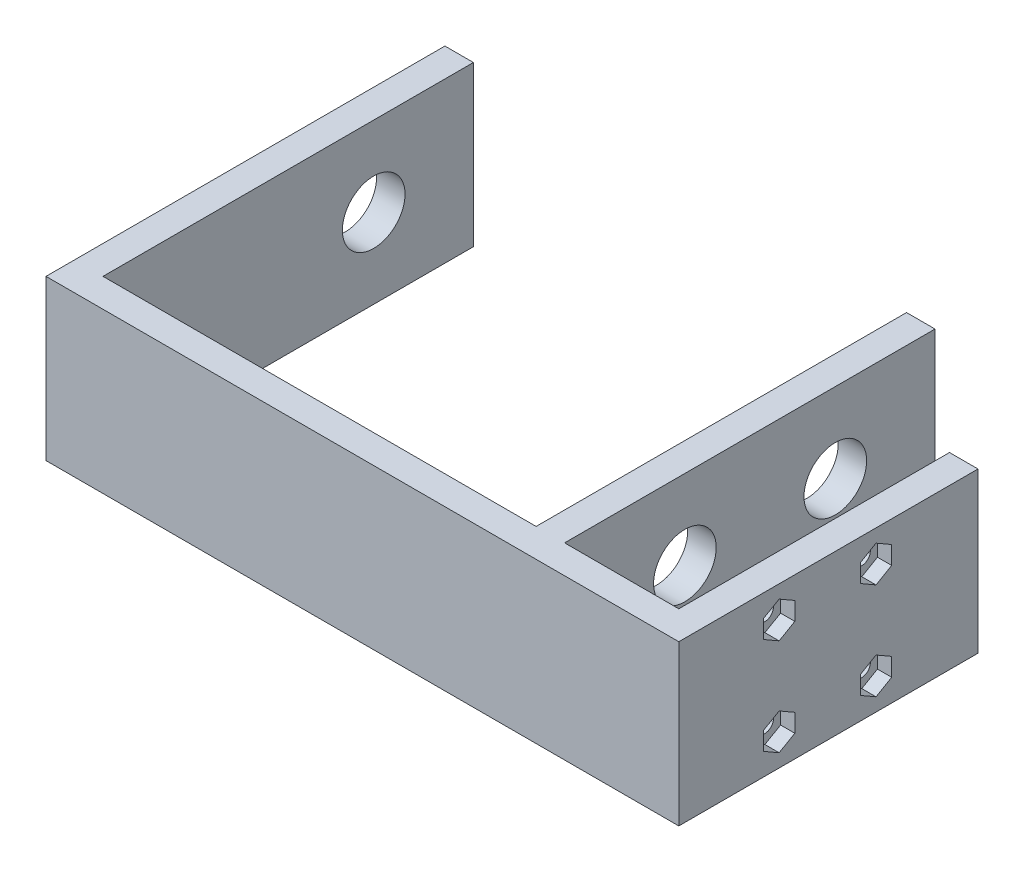
SolidWorks part; units mm, degrees
ref_plane "Front Plane" through (0, 0, 0) normal (0, 0, 1) x (1, 0, 0)
ref_plane "Top Plane" through (0, 0, 0) normal (0, 1, 0) x (1, 0, 0)
ref_plane "Right Plane" through (0, 0, 0) normal (1, 0, 0) x (0, 0, -1)
sketch "Sketch1" plane through (0, 0, 0) normal (0, 1, 0) x (1, 0, 0)
  line L0 (-35, -22.5) -> (-35, 22.5) construction
  line L1 (-30, -17.5) -> (30, -17.5) construction
  line L2 (-30, -17.5) -> (-30, 17.5) construction
  line L3 (-30, 17.5) -> (30, 17.5) construction
  line L4 (30, -17.5) -> (30, 17.5) construction
  line L5 (-30, -17.5) -> (30, 17.5) construction
  line L6 (-30, 17.5) -> (30, -17.5) construction
  line L7 (-35, 22.5) -> (35, 22.5) construction
  line L8 (35, -22.5) -> (35, 22.5) construction
  line L9 (-35, -22.5) -> (35, -22.5) construction
  line L10 (35, 0) -> (38, 0) construction
  line L11 (-35, 0) -> (-38, 0) construction
  line L12 (38, 0) -> (38, -22.5)
  line L13 (38, -22.5) -> (38, -47.5)
  line L14 (-38, 0) -> (-38, -22.5)
  line L15 (-38, -22.5) -> (-38, -47.5)
  line L16 (-38, -47.5) -> (38, -47.5)
  line L17 (38, 0) -> (38, 17.5)
  line L18 (-38, 0) -> (-38, 17.5)
  line L19 (-43, 0) -> (-43, 17.5)
  line L20 (-43, 0) -> (-43, -22.5)
  line L21 (-43, -22.5) -> (-43, -52.5)
  line L22 (-43, -52.5) -> (43, -52.5)
  line L23 (43, -22.5) -> (43, -52.5) construction
  line L24 (43, 0) -> (43, -22.5)
  line L25 (43, 0) -> (43, 17.5)
  line L26 (-38, 17.5) -> (-43, 17.5)
  line L27 (38, 17.5) -> (43, 17.5)
  line L28 (63.04, -47.5) -> (63.04, 0)
  line L29 (43, -52.5) -> (63.04, -52.5)
  line L31 (43, -47.5) -> (63.04, -47.5)
  line L32 (63.04, -52.5) -> (63.04, -47.5) construction
  line L33 (63.04, -52.5) -> (68.04, -52.5)
  line L34 (63.04, -52.5) -> (63.04, 0) construction
  line L35 (63.04, 0) -> (68.04, 0)
  line L36 (68.04, -52.5) -> (68.04, 0)
  line L37 (43, -47.5) -> (43, 17.5)
  point P0 (0, 0)
  point P10 (35, 0)
  point P11 (0, -22.5)
  point P12 (0, 22.5)
  point P13 (-35, 0)
  point P35 (0, 0)
  dimension "D1" = 60
  dimension "D2" = 35
  dimension "D4" = 3
  dimension "D5" = 25
  dimension "D7" = 20.04
  dimension "D8" = 5
  dimension "D3" = 5
  dimension "D6" = 5
extrude "Boss-Extrude1" add sketch "Sketch1" along normal mid plane 28 contours L31 L37 L24 L25 L27 L17 L12 L13 L16 L15 L14 L18 L26 L19 L20 L21 L22 L29 L33 L36 L35 L28 region at (39.3126, 0, -8.75)
sketch "Sketch2" plane through (43, 0, 0) normal (1, 0, 0) x (0, 0, -1)
  line L0 (-23.594, 0) -> (-26.9808, 0) construction
  line L1 (-23.594, 0) -> (-26.394, 0) construction
  line L4 (-47.5, -14) -> (17.5, -14)
  line L5 (17.5, -14) -> (17.5, 14)
  line L6 (-47.5, -14) -> (17.5, -14)
  line L7 (17.5, 14) -> (-47.5, 14)
  line L9 (17.5, -14) -> (17.5, 14)
  line L14 (17.5, 14) -> (-47.5, 14)
  line L15 (-47.5, 14) -> (-47.5, -14)
  line L16 (-47.5, 14) -> (-47.5, -14)
  circle A0 centre (0, 0) radius 5.5
  circle A1 centre (0, 0) radius 23.594 construction
  circle A2 centre (-26.394, 0) radius 3.3868 construction
  circle A3 centre (-26.9808, 0) radius 3.3867 construction
  circle A4 centre (-26.394, 0) radius 5.5
  dimension "D2" = 11
  dimension "D3" = 47.188
  dimension "D4" = 3.3868
  dimension "D5" = 2.8
  dimension "D1" = 0
extrude "Cut-Extrude1" cut sketch "Sketch2" against normal up to surface (86 mm away) contours A0 up to face at (-43, 0, 17.5)
sketch "Sketch3" plane through (43, 0, 0) normal (1, 0, 0) x (0, 0, -1)
  circle A0 centre (-26.394, 0) radius 5.5 construction
  circle A1 centre (-26.394, 0) radius 5.5
extrude "Cut-Extrude2" cut sketch "Sketch3" against normal up to next
sketch "Sketch4" plane through (63.04, 0, 0) normal (-1, 0, 0) x (0, 0, 1)
  line L1 (14.894, -11.5) -> (37.894, -11.5)
  line L2 (14.894, -11.5) -> (14.894, 11.5)
  line L3 (14.894, 11.5) -> (37.894, 11.5)
  line L4 (37.894, -11.5) -> (37.894, 11.5)
  line L5 (14.894, -11.5) -> (37.894, 11.5) construction
  line L6 (14.894, 11.5) -> (37.894, -11.5) construction
  line L7 (17.894, -8.5) -> (34.894, -8.5) construction
  line L8 (17.894, -8.5) -> (17.894, 8.5) construction
  line L9 (17.894, 8.5) -> (34.894, 8.5) construction
  line L10 (34.894, -8.5) -> (34.894, 8.5) construction
  line L11 (17.894, -8.5) -> (34.894, 8.5) construction
  line L12 (17.894, 8.5) -> (34.894, -8.5) construction
  circle A0 centre (17.894, 8.5) radius 1.85
  circle A1 centre (26.394, 0) radius 3
  circle A2 centre (26.394, 0) radius 3 construction
  circle A3 centre (34.894, 8.5) radius 1.85
  circle A4 centre (34.894, -8.5) radius 1.85
  circle A5 centre (17.894, -8.5) radius 1.85
  dimension "D6" = 3.7
  dimension "D2" = 23
  dimension "D3" = 23
  dimension "D4" = 17
  dimension "D5" = 17
  dimension "D1" = 0
sketch "Sketch6" plane through (68.04, 0, 0) normal (1, 0, 0) x (0, 0, -1)
  line L0 (-34.894, -5.2091) -> (-37.744, -6.8546) construction
  line L1 (-34.894, -5.3246) -> (-37.644, -6.9123)
  line L2 (-37.644, -6.9123) -> (-37.644, -10.0877)
  line L3 (-37.644, -10.0877) -> (-34.894, -11.6754)
  line L4 (-34.894, -11.6754) -> (-32.144, -10.0877)
  line L5 (-32.144, -10.0877) -> (-32.144, -6.9123)
  line L6 (-32.144, -6.9123) -> (-34.894, -5.3246)
  line L7 (-37.744, -6.8546) -> (-37.744, -10.1454) construction
  line L8 (-37.744, -10.1454) -> (-34.894, -11.7909) construction
  line L9 (-34.894, -11.7909) -> (-32.044, -10.1454) construction
  line L10 (-32.044, -10.1454) -> (-32.044, -6.8546) construction
  line L11 (-32.044, -6.8546) -> (-34.894, -5.2091) construction
  line L12 (-26.394, 1.435) -> (-26.394, -1.435) construction
  line L13 (-20.744, -6.8546) -> (-17.894, -5.2091) construction
  line L14 (-27.8, 0) -> (-24.988, 0) construction
  line L15 (-20.744, -10.1454) -> (-20.744, -6.8546) construction
  line L52 (-17.894, -11.7909) -> (-20.744, -10.1454) construction
  line L53 (-15.044, -10.1454) -> (-17.894, -11.7909) construction
  line L54 (-15.044, -6.8546) -> (-15.044, -10.1454) construction
  line L55 (-17.894, -5.2091) -> (-15.044, -6.8546) construction
  line L56 (-20.644, -6.9123) -> (-17.894, -5.3246)
  line L57 (-20.644, -10.0877) -> (-20.644, -6.9123)
  line L58 (-17.894, -11.6754) -> (-20.644, -10.0877)
  line L59 (-15.144, -10.0877) -> (-17.894, -11.6754)
  line L60 (-15.144, -6.9123) -> (-15.144, -10.0877)
  line L61 (-17.894, -5.3246) -> (-15.144, -6.9123)
  line L62 (-17.894, 5.2091) -> (-15.044, 6.8546) construction
  line L63 (-15.044, 6.8546) -> (-15.044, 10.1454) construction
  line L64 (-15.044, 10.1454) -> (-17.894, 11.7909) construction
  line L65 (-17.894, 11.7909) -> (-20.744, 10.1454) construction
  line L66 (-20.744, 10.1454) -> (-20.744, 6.8546) construction
  line L67 (-20.744, 6.8546) -> (-17.894, 5.2091) construction
  line L68 (-32.044, 6.8546) -> (-34.894, 5.2091) construction
  line L69 (-32.044, 10.1454) -> (-32.044, 6.8546) construction
  line L70 (-34.894, 11.7909) -> (-32.044, 10.1454) construction
  line L71 (-37.744, 10.1454) -> (-34.894, 11.7909) construction
  line L72 (-37.744, 6.8546) -> (-37.744, 10.1454) construction
  line L73 (-34.894, 5.2091) -> (-37.744, 6.8546) construction
  line L74 (-17.894, 5.3246) -> (-15.144, 6.9123)
  line L75 (-15.144, 6.9123) -> (-15.144, 10.0877)
  line L76 (-15.144, 10.0877) -> (-17.894, 11.6754)
  line L77 (-17.894, 11.6754) -> (-20.644, 10.0877)
  line L78 (-20.644, 10.0877) -> (-20.644, 6.9123)
  line L79 (-20.644, 6.9123) -> (-17.894, 5.3246)
  line L80 (-32.144, 6.9123) -> (-34.894, 5.3246)
  line L81 (-32.144, 10.0877) -> (-32.144, 6.9123)
  line L82 (-34.894, 11.6754) -> (-32.144, 10.0877)
  line L83 (-37.644, 10.0877) -> (-34.894, 11.6754)
  line L84 (-37.644, 6.9123) -> (-37.644, 10.0877)
  line L85 (-34.894, 5.3246) -> (-37.644, 6.9123)
  circle A3 centre (-34.894, -8.5) radius 1.85 construction
  circle A7 centre (-34.894, -8.5) radius 1.85 construction
  circle A8 centre (-34.894, -8.5) radius 2.75 construction
  circle A16 centre (-17.894, -8.5) radius 2.75 construction
  circle A17 centre (-17.894, -8.5) radius 1.85 construction
  circle A18 centre (-17.894, 8.5) radius 1.85 construction
  circle A19 centre (-17.894, 8.5) radius 2.75 construction
  circle A20 centre (-34.894, 8.5) radius 2.75 construction
  circle A21 centre (-34.894, 8.5) radius 1.85 construction
  point P29 (-26.394, 0)
  point P33 (-26.394, 0)
  dimension "D2" = 5.5
  dimension "D1" = 0.1
extrude "Cut-Extrude3" cut sketch "Sketch6" against normal blind 2.5
extrude "Boss-Extrude3" add sketch "Sketch4" along normal blind 1 contours A0 | A3 | A4 | A5 region at (63.04, 8.5, 17.894) region at (63.04, 8.5, 34.894) region at (63.04, -8.5, 34.894) region at (63.04, -8.5, 17.894)
sketch "Sketch7" plane through (62.04, 0, 0) normal (-1, 0, 0) x (0, 0, 1)
  circle A0 centre (34.894, 8.5) radius 1.5
  circle A1 centre (17.894, 8.5) radius 1.5
  circle A2 centre (34.894, -8.5) radius 1.85
  circle A3 centre (34.894, -8.5) radius 1.85
  circle A4 centre (17.894, 8.5) radius 1.85
  circle A5 centre (17.894, 8.5) radius 1.85
  circle A6 centre (17.894, -8.5) radius 1.85
  circle A7 centre (17.894, -8.5) radius 1.85
  circle A8 centre (17.894, -8.5) radius 1.5
  circle A9 centre (34.894, -8.5) radius 1.5
  dimension "D1" = 3
  dimension "D2" = 0
  dimension "D3" = 0
  dimension "D4" = 0
extrude "Cut-Extrude4" cut sketch "Sketch7" against normal up to next contours A8 | A9 | A0 | A1 region at (62.04, 8.5, 34.894) region at (62.04, -8.5, 17.894) region at (62.04, -8.5, 34.894)
equation "\"a\"= 1"
equation "\"b\"= 1"
equation "\"c\"= 1"
equation "\"d\"= 1"
equation "\"e\"= 1"
equation "\"x\"= 1"
equation "\"y\"= 1"
equation "\"z\"= 1"
